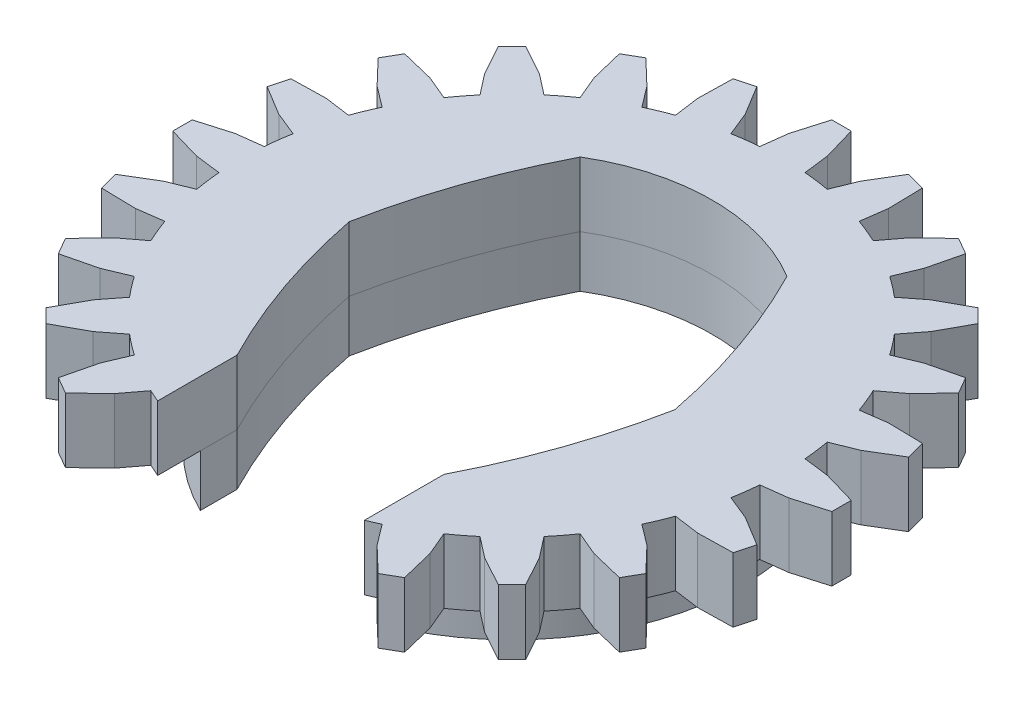
SolidWorks part; units mm, degrees
material "ABS"
ref_plane "Front Plane" through (0, 0, 0) normal (0, 0, 1) x (1, 0, 0)
ref_plane "Top Plane" through (0, 0, 0) normal (0, 1, 0) x (1, 0, 0)
ref_plane "Right Plane" through (0, 0, 0) normal (1, 0, 0) x (0, 0, -1)
ref_axis "Axis1" through (0, -0.225, 0) along (0, 1, 0)
sketch "Sketch1" plane through (0, 0, 0) normal (0, 1, 0) x (1, 0, 0)
  line L0 (0, -7.75) -> (0, 7.75) construction
  line L1 (-6.3, 0) -> (6.3, 0) construction
  line L5 (-4, -8.0623) -> (-4, -6.638)
  line L6 (4, -8.0623) -> (4, -6.638)
  arc A0 (-4, 6.638) -> (4, 6.638) centre (0, 0) cw
  arc A2 (-6.3, 0) -> (-4, 6.638) centre (18.2379, -4.7847) cw
  arc A5 (-4, -8.0623) -> (4, -8.0623) centre (0, 0) cw
  arc A6 (6.3, 0) -> (4, 6.638) centre (-18.2379, -4.7847) ccw
  arc A7 (6.3, 0) -> (4, -6.638) centre (-18.2379, 4.7847) cw
  arc A8 (-6.3, 0) -> (-4, -6.638) centre (18.2379, 4.7847) ccw
  dimension "D4" = 9
  dimension "D5" = 25
  dimension "D1" = 12.6
  dimension "D2" = 7.75
  dimension "D3" = 8
  dimension "D6" = 8
extrude "Boss-Extrude1" add sketch "Sketch1" along normal blind 2
sketch "Sketch2" plane through (0, 2, 0) normal (0, 1, 0) x (1, 0, 0)
  line L0 (4, -9.7082) -> (4, -8.0623)
  line L2 (-4, -8.0623) -> (-4, -6.638)
  line L3 (-4, -8.0623) -> (-4, -6.638)
  line L4 (-4, -9.7082) -> (-4, -8.0623)
  line L5 (4, -6.638) -> (4, -8.0623)
  line L6 (4, -6.638) -> (4, -8.0623)
  arc A0 (4, -9.7082) -> (-4, -9.7082) centre (0, 0) ccw
  arc A5 (6.3, 0) -> (4, 6.638) centre (-18.2379, -4.7847) ccw
  arc A6 (6.3, 0) -> (4, 6.638) centre (-18.2379, -4.7847) ccw
  arc A7 (-4, 6.638) -> (-6.3, 0) centre (18.2379, -4.7847) ccw
  arc A8 (-4, 6.638) -> (-6.3, 0) centre (18.2379, -4.7847) ccw
  arc A11 (-6.3, 0) -> (-4, -6.638) centre (18.2379, 4.7847) ccw
  arc A12 (4, -8.0623) -> (-4, -8.0623) centre (0, 0) ccw
  arc A13 (-6.3, 0) -> (-4, -6.638) centre (18.2379, 4.7847) ccw
  arc A14 (4, 6.638) -> (-4, 6.638) centre (0, 0) ccw
  arc A15 (4, -6.638) -> (6.3, 0) centre (-18.2379, 4.7847) ccw
  arc A16 (4, -6.638) -> (6.3, 0) centre (-18.2379, 4.7847) ccw
  arc A18 (4, 6.638) -> (-4, 6.638) centre (0, 0) ccw
  dimension "D4" = 10.5
  dimension "D3" = 0
extrude "Boss-Extrude2" add sketch "Sketch2" along normal blind 2.5 separate body
sketch "Sketch7" plane through (0, 4.5, 0) normal (0, 1, 0) x (1, 0, 0)
  line L0 (0, 10.5) -> (0, 12.75) construction
  line L1 (-0.375, 12.75) -> (0.375, 12.75)
  line L2 (0.375, 12.75) -> (0.75, 11.4624)
  line L3 (0.75, 11.4624) -> (0.875, 10.4635)
  line L4 (-0.75, 11.4624) -> (-0.875, 10.4635)
  line L5 (-0.375, 12.75) -> (-0.75, 11.4624)
  arc A0 (4, -9.7082) -> (-4, -9.7082) centre (0, 0) ccw construction
  arc A1 (0.875, 10.4635) -> (-0.875, 10.4635) centre (0, 0) ccw
  dimension "D1" = 0.375
  dimension "D2" = 2.25
  dimension "D3" = 0.875
  dimension "D4" = 0.75
extrude "Boss-Extrude5" add sketch "Sketch7" against normal up to surface (2.5 mm away) up to face at (0, 2, -0.238)
pattern_circular "CirPattern2" count 24 over 360 about axis through (0, -0.225, 0) along (0, 1, 0) skipping 11, 12, 13 of "Boss-Extrude5"
